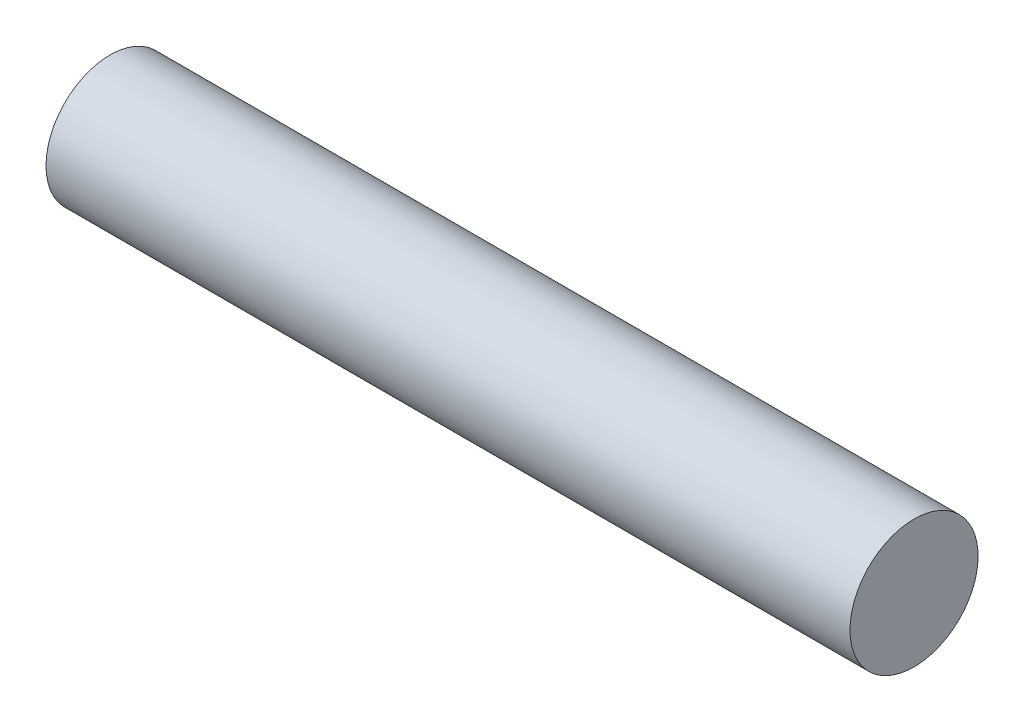
SolidWorks part; units mm, degrees
ref_plane "Front Plane" through (0, 0, 0) normal (0, 0, 1) x (1, 0, 0)
ref_plane "Top Plane" through (0, 0, 0) normal (0, 1, 0) x (1, 0, 0)
ref_plane "Right Plane" through (0, 0, 0) normal (1, 0, 0) x (0, 0, -1)
sketch "Sketch2" plane through (0, 0, 0) normal (0, 1, 0) x (1, 0, 0)
  line L0 (0, 0) -> (800, 0)
  line L1 (800, 0) -> (800, 63.75)
  line L2 (800, 63.75) -> (0, 63.75)
  line L3 (0, 63.75) -> (0, 0)
revolve "Revolve1" add sketch "Sketch2" angle 360 about L2 reverse direction yes
